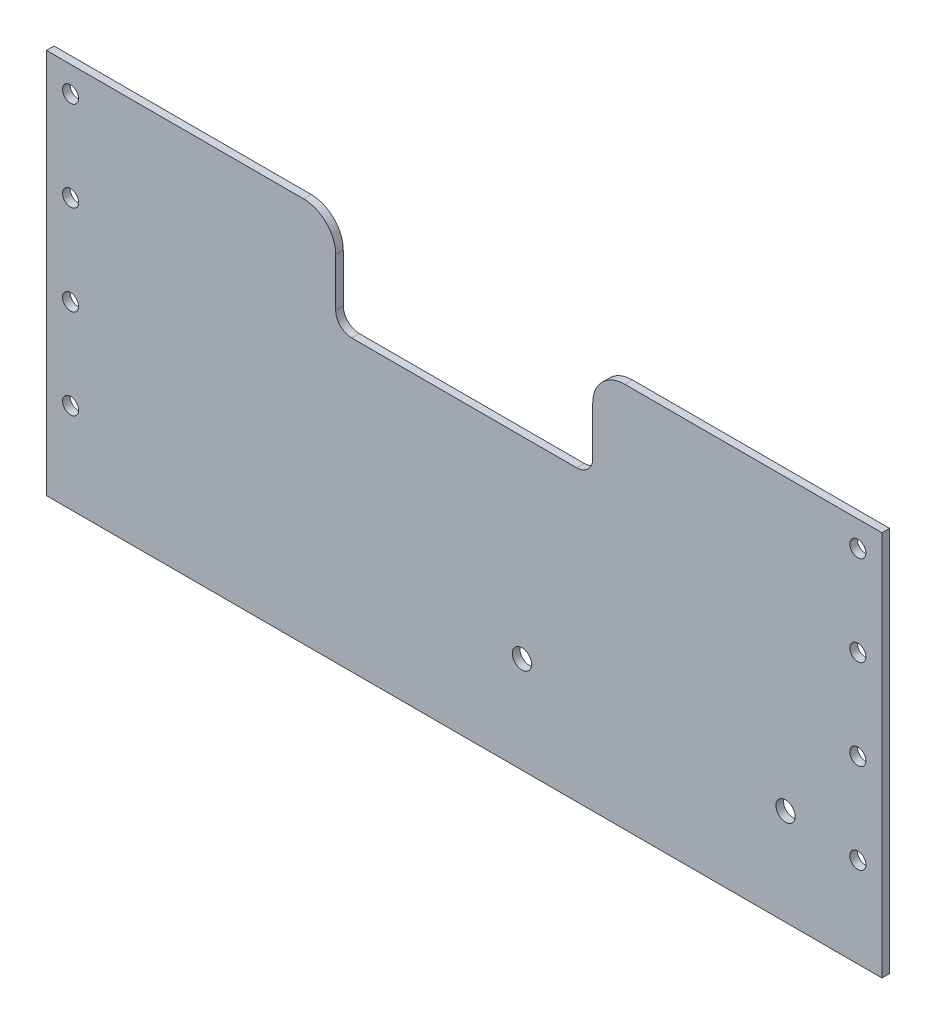
SolidWorks part; units mm, degrees
material "Thornel VCB-20 Carbon Cloth"
ref_plane "Front Plane" through (0, 0, 0) normal (0, 0, 1) x (1, 0, 0)
ref_plane "Top Plane" through (0, 0, 0) normal (0, 1, 0) x (1, 0, 0)
ref_plane "Right Plane" through (0, 0, 0) normal (1, 0, 0) x (0, 0, -1)
sketch "Sketch1" plane through (0, 0, 0) normal (0, 0, 1) x (1, 0, 0)
  line L0 (0, -58.42) -> (0, 58.42) construction
  line L2 (-82.55, 55.7897) -> (-82.55, -52.07)
  line L3 (-76.2, -58.42) -> (76.2, -58.42)
  line L4 (82.55, 55.7897) -> (82.55, -52.07)
  line L5 (-82.55, 58.42) -> (82.55, -58.42) construction
  line L6 (-82.55, -58.42) -> (82.55, 58.42) construction
  line L7 (-80.6901, 60.2799) -> (-75.4296, 65.5404)
  line L8 (-70.9395, 67.4003) -> (-50.8, 67.4003)
  line L9 (-46.3099, 65.5404) -> (-41.0494, 60.2799)
  line L10 (46.3099, 65.5404) -> (41.0494, 60.2799)
  line L11 (70.9395, 67.4003) -> (50.8, 67.4003)
  line L12 (80.6901, 60.2799) -> (75.4296, 65.5404)
  line L13 (-73.5697, 67.4003) -> (-82.55, 67.4003) construction
  line L14 (-82.55, 67.4003) -> (-82.55, 58.42) construction
  line L15 (-36.5592, 58.42) -> (0, 58.42)
  line L16 (0, 58.42) -> (36.5592, 58.42)
  circle A0 centre (-77.7875, -35.052) radius 1.5875
  circle A1 centre (-77.7875, -11.684) radius 1.5875
  circle A2 centre (-77.7875, 11.684) radius 1.5875
  circle A3 centre (-77.7875, 35.052) radius 1.5875
  circle A4 centre (77.7875, 35.052) radius 1.5875
  circle A5 centre (77.7875, 11.684) radius 1.5875
  circle A6 centre (77.7875, -11.684) radius 1.5875
  circle A7 centre (77.7875, -35.052) radius 1.5875
  arc A8 (82.55, 55.7897) -> (80.6901, 60.2799) centre (76.2, 55.7897) ccw
  arc A9 (75.4296, 65.5404) -> (70.9395, 67.4003) centre (70.9395, 61.0503) ccw
  arc A10 (46.3099, 65.5404) -> (50.8, 67.4003) centre (50.8, 61.0503) cw
  arc A11 (41.0494, 60.2799) -> (36.5592, 58.42) centre (36.5592, 64.77) cw
  arc A12 (-36.5592, 58.42) -> (-41.0494, 60.2799) centre (-36.5592, 64.77) cw
  arc A13 (-46.3099, 65.5404) -> (-50.8, 67.4003) centre (-50.8, 61.0503) ccw
  arc A14 (-70.9395, 67.4003) -> (-75.4296, 65.5404) centre (-70.9395, 61.0503) ccw
  arc A15 (-82.55, 55.7897) -> (-80.6901, 60.2799) centre (-76.2, 55.7897) cw
  arc A16 (76.2, -58.42) -> (82.55, -52.07) centre (76.2, -52.07) ccw
  arc A17 (-76.2, -58.42) -> (-82.55, -52.07) centre (-76.2, -52.07) cw
  circle A18 centre (-70.9395, 61.0503) radius 1.5875
  circle A19 centre (-50.8, 61.0503) radius 1.5875
  circle A20 centre (50.8, 61.0503) radius 1.5875
  circle A21 centre (70.9395, 61.0503) radius 1.5875
  point P0 (0, 0)
  point P36 (73.5697, 67.4003)
  point P39 (48.1697, 67.4003)
  point P42 (39.1895, 58.42)
  point P45 (-39.1895, 58.42)
  point P48 (-48.1697, 67.4003)
  dimension "D3" = 3.175
  dimension "D11" = 6.35
  dimension "D12" = 6.35
  dimension "D13" = 3.175
  dimension "D14" = 3.175
  dimension "D1" = 165.1
  dimension "D2" = 116.84
  dimension "D4" = 23.368
  dimension "D5" = 4.7625
  dimension "D7" = 46.736
  dimension "D8" = 12.7
  dimension "D9" = 135
  dimension "D10" = 25.4
  dimension "D6" = 4
extrude "Boss-Extrude1" [suppressed] add sketch "Sketch1" along normal blind 1.5
sketch "Sketch2" [suppressed] plane through (0, 0, 1.5) normal (0, 0, 1) x (1, 0, 0)
  line L0 (0, -45.72) -> (0, 6.3634) construction
  line L1 (0, -58.42) -> (0, 63.5) construction
  line L3 (-82.55, 1.8599) -> (82.55, 1.8599) construction
  line L4 (-82.55, 55.7897) -> (-82.55, -52.07) construction
  line L5 (82.55, -52.07) -> (82.55, 55.7897) construction
  line L7 (-76.2, -58.42) -> (76.2, -58.42) construction
  circle A0 centre (0, -45.72) radius 1.9062
  circle A1 centre (0, 6.3634) radius 1.9062
  dimension "D2" = 3.8125
  dimension "D3" = 3.8125
  dimension "D1" = 52.0834
  dimension "D4" = 12.7
extrude "Cut-Extrude1" [suppressed] cut sketch "Sketch2" against normal through all
sketch "Sketch3" [suppressed] plane through (0, 0, 1.5) normal (0, 0, 1) x (1, 0, 0)
  line L0 (0, 50.8) -> (0, 30.8) construction
  line L1 (-10, 40.8) -> (10, 40.8) construction
  line L2 (-10, 40.8) -> (0, 50.8) construction
  line L3 (0, 50.8) -> (10, 40.8) construction
  line L4 (10, 40.8) -> (0, 30.8) construction
  line L5 (0, 30.8) -> (-10, 40.8) construction
  line L6 (0, 63.5) -> (0, -58.42) construction
  line L8 (-76.2, -58.42) -> (76.2, -58.42) construction
  circle A0 centre (0, 50.8) radius 1.8669
  circle A1 centre (-10, 40.8) radius 1.8669
  circle A2 centre (0, 30.8) radius 1.8669
  circle A3 centre (10, 40.8) radius 1.8669
  dimension "D1" = 3.7338
  dimension "D2" = 12.7
extrude "Cut-Extrude2" [suppressed] cut sketch "Sketch3" against normal through all
sketch "Sketch4" [suppressed] plane through (0, 0, 1.5) normal (0, 0, 1) x (1, 0, 0)
  line L0 (0, 58.42) -> (0, -58.42) construction
  line L1 (36.5592, 58.42) -> (-36.5592, 58.42) construction
  line L2 (-76.2, -58.42) -> (76.2, -58.42) construction
  line L5 (0, 33.045) -> (0, 52.045) construction
  line L6 (-9.5, 42.545) -> (9.5, 42.545) construction
  circle A14 centre (0, 42.545) radius 8 construction
  circle A15 centre (0, 42.545) radius 9.5 construction
  circle A16 centre (0, 50.545) radius 1.5
  circle A17 centre (0, 34.545) radius 1.5
  circle A18 centre (-9.5, 42.545) radius 1.5
  circle A19 centre (9.5, 42.545) radius 1.5
  dimension "D1" = 15.875
  dimension "D3" = 16
  dimension "D4" = 19
  dimension "D5" = 3
  dimension "D6" = 3
  dimension "D7" = 3
  dimension "D8" = 3
extrude "Cut-Extrude3" [suppressed] cut sketch "Sketch4" against normal through all
sketch "Sketch5" plane through (0, 0, 0) normal (0, 0, 1) x (1, 0, 0)
  line L0 (0, -58.337) -> (0, 30.563) construction
  line L1 (-43.2483, 30.563) -> (43.2483, 30.563) construction
  line L2 (-82.55, 17.863) -> (-82.55, -58.337)
  line L3 (-82.55, -58.337) -> (82.55, -58.337)
  line L4 (82.55, 17.863) -> (82.55, -58.337)
  line L5 (-43.2483, 30.563) -> (82.55, -58.337) construction
  line L6 (-82.55, -58.337) -> (43.2483, 30.563) construction
  line L7 (-77.7875, -58.337) -> (-77.7875, 30.563) construction
  line L8 (-77.7875, -40.557) -> (-77.7875, -22.777) construction
  line L9 (77.7875, -58.337) -> (77.7875, 30.563) construction
  line L11 (11.4166, -39.287) -> (63.5, -39.287) construction
  line L13 (-82.55, -0.6801) -> (82.55, -0.6801) construction
  line L14 (-82.55, 17.863) -> (-31.75, 17.863)
  line L15 (-22.225, -1.187) -> (22.225, -1.187)
  line L16 (-25.4, 1.988) -> (-25.4, 11.513)
  line L17 (25.4, 1.988) -> (25.4, 11.513)
  line L18 (31.75, 17.863) -> (82.55, 17.863)
  circle A0 centre (-77.7875, -40.557) radius 1.5875
  circle A1 centre (-77.7875, -22.777) radius 1.5875
  circle A2 centre (-77.7875, -4.997) radius 1.5875
  circle A3 centre (-77.7875, 12.783) radius 1.5875
  circle A8 centre (11.4166, -39.287) radius 1.9062
  circle A9 centre (63.5, -39.287) radius 1.9062
  circle A10 centre (21.1667, -9.332) radius 1.5875 construction
  circle A11 centre (-21.1667, -9.332) radius 1.5875 construction
  arc A12 (-25.4, 11.513) -> (-31.75, 17.863) centre (-31.75, 11.513) ccw
  arc A13 (25.4, 11.513) -> (31.75, 17.863) centre (31.75, 11.513) cw
  arc A14 (25.4, 1.988) -> (22.225, -1.187) centre (22.225, 1.988) cw
  arc A15 (-25.4, 1.988) -> (-22.225, -1.187) centre (-22.225, 1.988) ccw
  circle A16 centre (77.7875, 12.783) radius 1.5875
  circle A17 centre (77.7875, -4.997) radius 1.5875
  circle A18 centre (77.7875, -22.777) radius 1.5875
  circle A19 centre (77.7875, -40.557) radius 1.5875
  point P0 (0, 0)
  point P52 (25.4, 17.863)
  point P55 (25.4, -1.187)
  point P58 (-25.4, -1.187)
  point P59 (0, -1.187)
  dimension "D6" = 4
  dimension "D4" = 3.175
  dimension "D12" = 3.175
  dimension "D13" = 3.175
  dimension "D17" = 6.35
  dimension "D18" = 6.35
  dimension "D19" = 3.175
  dimension "D20" = 3.175
  dimension "D22" = 3.8125
  dimension "D23" = 3.8125
  dimension "D2" = 165.1
  dimension "D3" = 4.7625
  dimension "D5" = 17.78
  dimension "D7" = 17.78
  dimension "D8" = 39.895
  dimension "D9" = 39.895
  dimension "D10" = 61.3833
  dimension "D11" = 61.3833
  dimension "D14" = 12.7
  dimension "D15" = 50.8
  dimension "D16" = 19.05
  dimension "D21" = 52.0834
  dimension "D25" = 88.9
  dimension "D24" = 19.05
  dimension "D26" = 19.05
extrude "Boss-Extrude2" add sketch "Sketch5" along normal blind 1.5
equation "\"Top Plate Width\" = 4.5in"
equation "\"Plate Width\" = 3.5in"
equation "\"Plate Thickness\" = 0.375in"
equation "\"Num holes\" = 4"
equation "\"Plate Height\" = 1.25in"
equation "\"Plate Clearance Hole Diameter\" = 0.125in"
equation "\"D3@Sketch1\"=\"Plate Clearance Hole Diameter\""
equation "\"Hole Spacing\"= \"Plate Width\" / ( \"Num holes\" + 1 )"
equation "\"Plate Tap Hole Diameter\" = 0.116in"
equation "\"Bottom Plate Length\" = 6.5in"
equation "\"D2@Sketch5\"=\"Bottom Plate Length\""
equation "\"D3@Sketch5\"=\"Plate Thickness\"/2"
equation "\"D4@Sketch5\"=\"Plate Clearance Hole Diameter\""
equation "\"D5@Sketch5\"=(\"Plate Width\" )/ ( \"Num holes\" + 1 )"
equation "\"D6@Sketch5\"=\"Num holes\""
equation "\"D7@Sketch5\"=\"Plate Width\"/ ( \"Num holes\" + 1 )"
equation "\"D12@Sketch5\"=\"Plate Clearance Hole Diameter\""
equation "\"D13@Sketch5\"=\"Plate Clearance Hole Diameter\""
equation "\"D25@Sketch5\"=\"Plate Width\""
